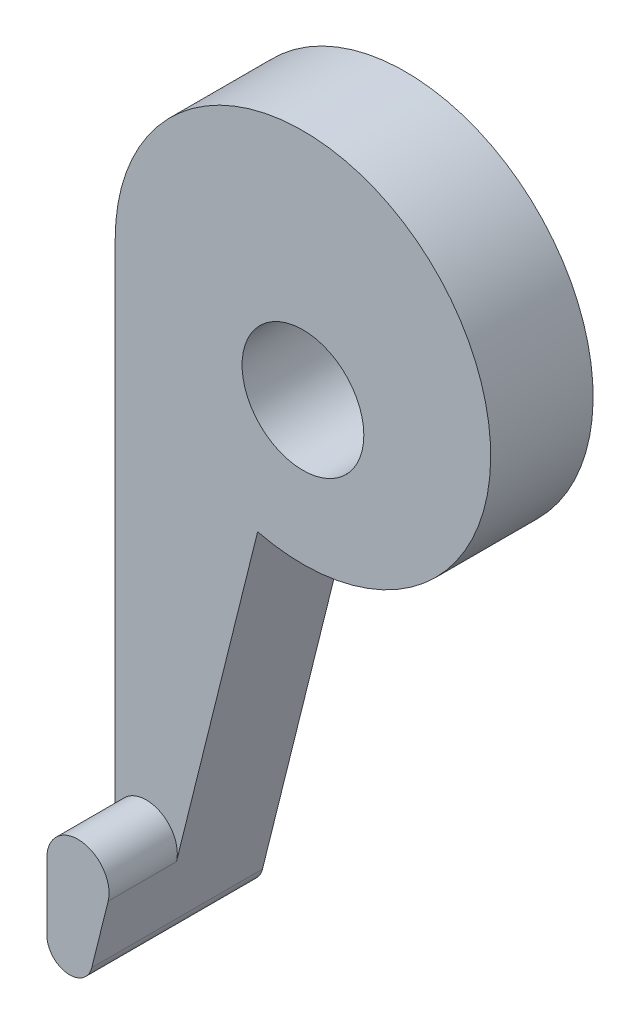
SolidWorks part; units mm, degrees
ref_plane "Front Plane" through (0, 0, 0) normal (0, 0, 1) x (1, 0, 0)
ref_plane "Top Plane" through (0, 0, 0) normal (0, 1, 0) x (1, 0, 0)
ref_plane "Right Plane" through (0, 0, 0) normal (1, 0, 0) x (0, 0, -1)
ref_axis "X-Axis" through (0, 0, 0) along (1, 0, 0)
ref_axis "Y-Axis" through (0, 42.2917, 0) along (0, -1, 0)
ref_axis "Z-Axis" through (0, 0, 55.0015) along (0, 0, -1)
sketch "Sketch1" plane through (0, 0, 0) normal (0, 0, 1) x (1, 0, 0)
  line L0 (1.3355, 8.5187) -> (1.3355, -16.4813)
  line L1 (3.3059, -16.7227) -> (7.5938, 0.5128)
  line L2 (9.5855, 8.5187) -> (9.5855, 6.5187) construction
  circle A0 centre (9.5855, 8.5187) radius 8.25 construction
  circle A1 centre (9.5855, 6.5187) radius 2.675
  arc A2 (1.3355, -16.4813) -> (3.3059, -16.7227) centre (2.3355, -16.4813) ccw
  arc A3 (7.5938, 0.5128) -> (1.3355, 8.5187) centre (9.5855, 8.5187) ccw
  dimension "D2" = 5.35
  dimension "D3" = 16.5
  dimension "D5" = 1
  dimension "D1" = 2
  dimension "D4" = 25
  dimension "D6" = 13.97
extrude "Boss-Extrude1" add sketch "Sketch1" along normal blind 4.5
sketch "Sketch2" plane through (0, 0, 4.5) normal (0, 0, 1) x (1, 0, 0)
  line L0 (1.3355, 8.5187) -> (1.3355, -16.4813) construction
  line L1 (3.3059, -16.7227) -> (7.5938, 0.5128) construction
  line L2 (1.3355, -13.5035) -> (1.3355, -16.4813)
  line L3 (3.3059, -16.7227) -> (4.0248, -13.833)
  arc A1 (1.3355, -13.5035) -> (4.0248, -13.833) centre (2.7003, -13.5035) cw
  arc A2 (1.3355, -16.4813) -> (3.3059, -16.7227) centre (2.3355, -16.4813) ccw
  dimension "D1" = 3
extrude "Boss-Extrude2" add sketch "Sketch2" along normal blind 3
